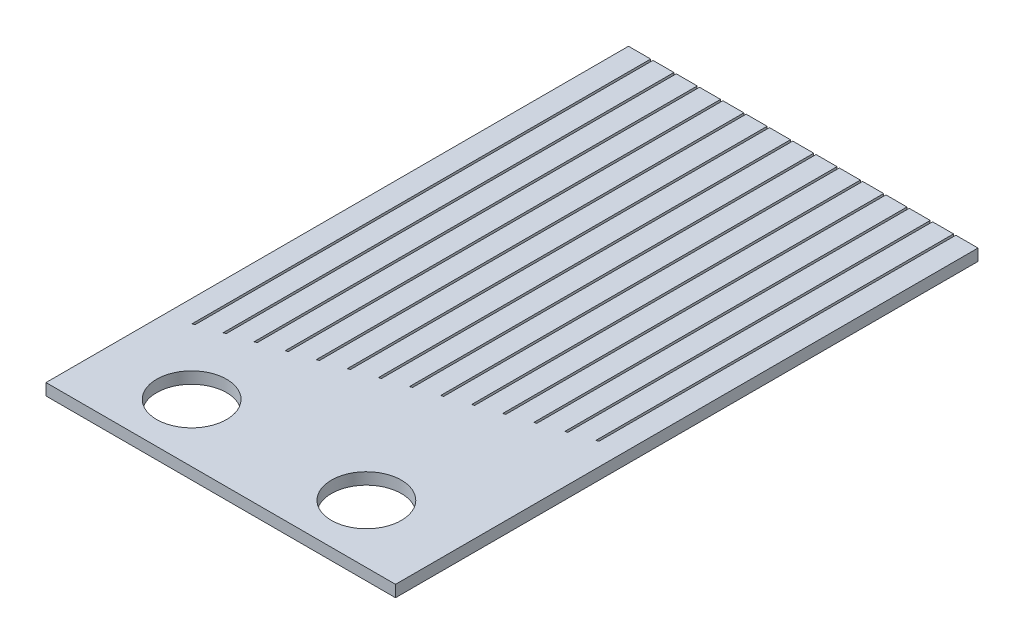
SolidWorks part; units mm, degrees
ref_plane "Front" through (0, 0, 0) normal (0, 0, 1) x (1, 0, 0)
ref_plane "Top" through (0, 0, 0) normal (0, 1, 0) x (1, 0, 0)
ref_plane "Right" through (0, 0, 0) normal (1, 0, 0) x (0, 0, -1)
sketch "Sketch1" plane through (0, 0, 0) normal (0, 1, 0) x (1, 0, 0)
  line L0 (-7.5, -7.5) -> (7.5, -2.5)
  line L1 (-7.5, -12.5) -> (7.5, -12.5)
  line L2 (-7.5, -12.5) -> (-7.5, 12.5)
  line L3 (-7.5, 12.5) -> (7.5, 12.5)
  line L4 (7.5, -12.5) -> (7.5, 12.5)
  line L5 (-7.5, -12.5) -> (7.5, 12.5) construction
  line L6 (-7.5, 12.5) -> (7.5, -12.5) construction
  line L7 (-6.55, -7.1833) -> (-6.55, 12.5)
  line L8 (-6.45, -7.15) -> (-6.45, 12.5)
  line L9 (-5.55, -6.85) -> (-5.55, 12.5)
  line L10 (-5.45, -6.8167) -> (-5.45, 12.5)
  line L11 (-4.55, -6.5167) -> (-4.55, 12.5)
  line L12 (-4.45, -6.4833) -> (-4.45, 12.5)
  line L13 (-3.55, -6.1833) -> (-3.55, 12.5)
  line L14 (-3.45, -6.15) -> (-3.45, 12.5)
  line L15 (-2.55, -5.85) -> (-2.55, 12.5)
  line L16 (-2.45, -5.8167) -> (-2.45, 12.5)
  line L17 (-1.55, -5.5167) -> (-1.55, 12.5)
  line L18 (-1.45, -5.4833) -> (-1.45, 12.5)
  line L19 (-0.55, -5.1833) -> (-0.55, 12.5)
  line L20 (0.45, -4.85) -> (0.45, 12.5)
  line L21 (1.45, -4.5167) -> (1.45, 12.5)
  line L22 (2.45, -4.1833) -> (2.45, 12.5)
  line L23 (1.55, -4.4833) -> (1.55, 12.5)
  line L24 (2.55, -4.15) -> (2.55, 12.5)
  line L25 (0.55, -4.8167) -> (0.55, 12.5)
  line L26 (-0.45, -5.15) -> (-0.45, 12.5)
  line L27 (3.45, -3.85) -> (3.45, 12.5)
  line L28 (4.45, 12.5) -> (4.45, -3.5167)
  line L29 (5.45, 12.5) -> (5.45, -3.1833)
  line L30 (5.55, 12.5) -> (5.55, -3.15)
  line L31 (4.55, 12.5) -> (4.55, -3.4833)
  line L32 (3.55, 12.5) -> (3.55, -3.8167)
  line L33 (6.45, 12.5) -> (6.45, -2.85)
  line L34 (6.55, 12.5) -> (6.55, -2.8167)
  circle A0 centre (-3.75, -10) radius 1.5
  circle A1 centre (3.75, -10) radius 1.5
  point P0 (0, 0)
  dimension "D33" = 3
  dimension "D36" = 2
  dimension "D1" = 15
  dimension "D2" = 25
  dimension "D3" = 5
  dimension "D4" = 10
  dimension "D5" = 0.95
  dimension "D6" = 0.1
  dimension "D7" = 0.9
  dimension "D8" = 0.1
  dimension "D9" = 0.9
  dimension "D10" = 0.1
  dimension "D11" = 0.9
  dimension "D12" = 0.1
  dimension "D13" = 0.9
  dimension "D14" = 0.1
  dimension "D15" = 0.9
  dimension "D16" = 0.1
  dimension "D17" = 0.9
  dimension "D18" = 0.1
  dimension "D19" = 0.9
  dimension "D20" = 0.1
  dimension "D21" = 0.9
  dimension "D22" = 0.1
  dimension "D23" = 0.9
  dimension "D24" = 0.1
  dimension "D25" = 0.9
  dimension "D26" = 0.1
  dimension "D27" = 0.9
  dimension "D28" = 0.1
  dimension "D29" = 0.9
  dimension "D30" = 0.1
  dimension "D31" = 0.9
  dimension "D32" = 0.1
  dimension "D34" = 2.5
  dimension "D35" = 3.75
extrude "Boss-Extrude1" add sketch "Sketch1" along normal blind 0.5 contours L1 L4 L0 L2 A1 A0 | L3 L34 L0 L4 | L33 L3 L30 L0 | L3 L31 L0 L29 | L3 L32 L0 L28 | L0 L27 L3 L24 | L23 L0 L22 L3 | L25 L0 L21 L3 | L26 L0 L20 L3 | L0 L19 L3 L18 | L0 L17 L3 L16 | L0 L15 L3 L14 | L0 L13 L3 L12 | L0 L11 L3 L10 | L0 L9 L3 L8 | L0 L7 L3 L2 region at (-7.0263, 0, -2.579) region at (0.9531, 0, 8.4115) region at (-6.0012, 0, -2.7498) region at (7.0233, 0, -4.9206) region at (-5.0012, 0, -2.9165) region at (5.9985, 0, -4.7498) region at (-4.0012, 0, -3.0831) region at (4.9986, 0, -4.5831) region at (-3.0012, 0, -3.2498) region at (3.9986, 0, -4.4164) region at (-2.0012, 0, -3.4165) region at (2.9986, 0, -4.2498) region at (-1.0013, 0, -3.5831) region at (1.9987, 0, -4.0831) region at (-0.0013, 0, -3.7498) region at (0.9987, 0, -3.9164)
